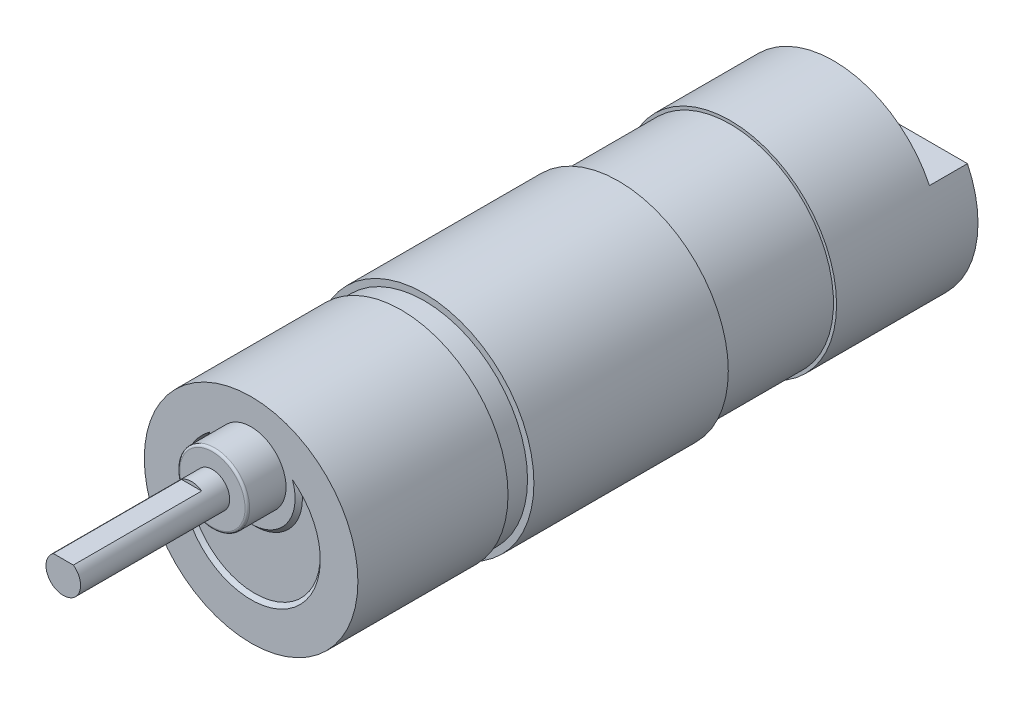
SolidWorks part; units mm, degrees
material "Cast Alloy Steel"
ref_plane "Front Plane" through (0, 0, 0) normal (0, 0, 1) x (1, 0, 0)
ref_plane "Top Plane" through (0, 0, 0) normal (0, 1, 0) x (1, 0, 0)
ref_plane "Right Plane" through (0, 0, 0) normal (1, 0, 0) x (0, 0, -1)
sketch "Sketch1" plane through (0, 0, 0) normal (0, 0, 1) x (1, 0, 0)
  circle A0 centre (0, 0) radius 18.5039
  dimension "D1" = 37.0078
extrude "Gearbox" add sketch "Sketch1" against normal blind 26.0096
sketch "Sketch2" plane through (0, 0, -26.0096) normal (0, 0, -1) x (-1, 0, 0)
  circle A0 centre (0, 0) radius 17.8943
  dimension "D1" = 35.7886
extrude "Boss-Extrude2" add sketch "Sketch2" along normal blind 56.9976
ref_plane "Wrap Start" through (0, 0, -29.9974) normal (0, 0, -1) x (-1, 0, 0)
sketch "Sketch3" plane through (0, 0, -29.9974) normal (0, 0, -1) x (-1, 0, 0)
  circle A0 centre (0, 0) radius 18.9992
  dimension "D1" = 37.9984
extrude "Wrap" add sketch "Sketch3" along normal blind 33.6804
sketch "Sketch4" plane through (0, 0, -83.0072) normal (0, 0, -1) x (-1, 0, 0)
  circle A0 centre (0, 0) radius 18.4277
  dimension "D1" = 36.8554
extrude "Boss-Extrude4" add sketch "Sketch4" along normal blind 24.5016
sketch "Connector" plane through (0, 0, -107.5088) normal (0, 0, -1) x (-1, 0, 0)
  line L0 (0, 0) -> (0, 8.001) construction
  line L1 (0, 8.001) -> (16.6001, 8.001)
  line L3 (0, 8.001) -> (-16.6001, 8.001)
  circle A2 centre (0, 0) radius 18.4277 construction
  arc A3 (-16.6001, 8.001) -> (16.6001, 8.001) centre (0, 0) cw
  point P8 (0, 8.001)
  point P9 (0, 8.001)
  dimension "D1" = 8.001
extrude "Connectdor Cut" cut sketch "Connector" against normal blind 6.5786
sketch "Sketch6" plane through (0, 0, 0) normal (0, 0, 1) x (1, 0, 0)
  circle A0 centre (0, 0) radius 11.9888
  dimension "D1" = 23.9776
extrude "Center DIsh" cut sketch "Sketch6" against normal blind 0.635
sketch "Sketch7" plane through (0, 0, -0.635) normal (0, 0, 1) x (1, 0, 0)
  line L0 (0, 0) -> (0, 7.0104) construction
  circle A0 centre (0, 7.0104) radius 7.62
  dimension "D2" = 15.24
  dimension "D1" = 7.0104
extrude "Boss-Extrude5" add sketch "Sketch7" along normal blind 0.635
chamfer "Chamfer4" distance 0.635 angle 45 1 edges at (0, -0.6096, -0.635)
chamfer "Chamfer5" distance 0.635 angle 45 1 edges at (0, -11.9888, -0.635)
sketch "Sketch8" plane through (0, 0, 0) normal (0, 0, 1) x (1, 0, 0)
  circle A0 centre (0, 7.9216) radius 6.0515
  dimension "D1" = 12.1031
extrude "Shaft Collar" add sketch "Sketch8" along normal blind 6.7056
fillet "Fillet1" radius 0.3969 1 edges at (6.0515, 7.9216, 6.7056)
sketch "Sketch9" plane through (0, 0, 6.7056) normal (0, 0, 1) x (1, 0, 0)
  circle A0 centre (0, 7.9216) radius 2.9972
  dimension "D1" = 5.9944
extrude "Boss-Extrude7" add sketch "Sketch9" along normal blind 25.8318
sketch "Sketch10" plane through (0, 0, 32.5374) normal (0, 0, 1) x (1, 0, 0)
  line L0 (0, 7.9216) -> (0, 10.36) construction
  line L1 (0, 10.36) -> (-1.7428, 10.36)
  line L2 (0, 10.36) -> (1.7428, 10.36)
  circle A0 centre (0, 7.9216) radius 2.9972 construction
  arc A1 (-1.7428, 10.36) -> (1.7428, 10.36) centre (0, 7.9216) cw
  dimension "D1" = 2.4384
extrude "Cut-Extrude3" cut sketch "Sketch10" against normal blind 22.225
